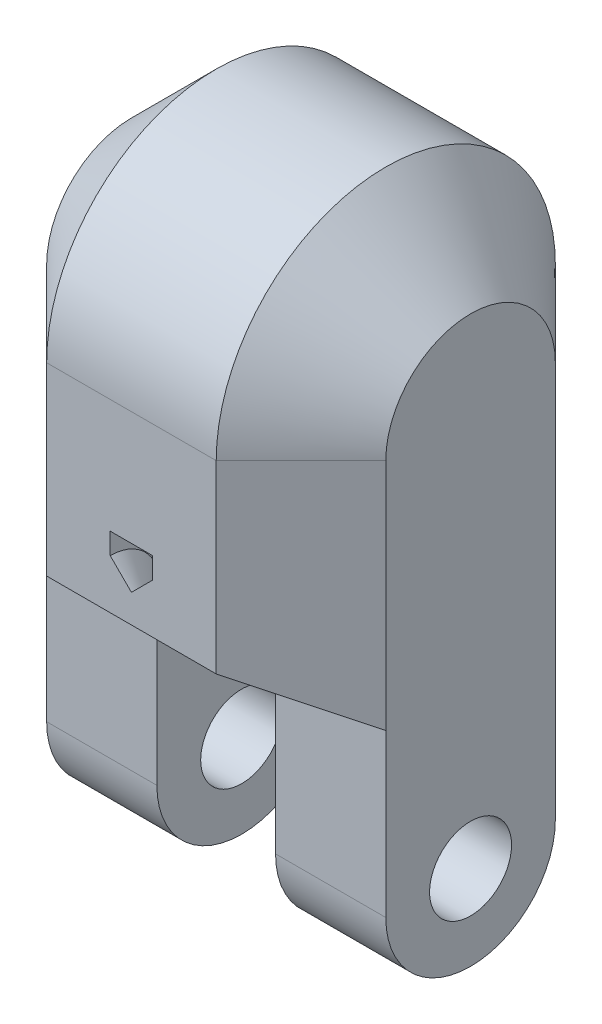
SolidWorks part; units mm, degrees
ref_plane "Front Plane" through (0, 0, 0) normal (0, 0, 1) x (1, 0, 0)
ref_plane "Top Plane" through (0, 0, 0) normal (0, 1, 0) x (1, 0, 0)
ref_plane "Right Plane" through (0, 0, 0) normal (1, 0, 0) x (0, 0, -1)
sketch "Sketch2" plane through (0, 0, 0) normal (0, 1, 0) x (1, 0, 0)
  line L0 (-3, 6) -> (3, 6)
  line L1 (3, 6) -> (6, 3)
  line L2 (6, 3) -> (6, -3)
  line L3 (6, -3) -> (3, -6)
  line L4 (3, -6) -> (-3, -6)
  line L5 (-3, -6) -> (-6, -3)
  line L6 (-6, -3) -> (-6, 3)
  line L7 (-6, 3) -> (-3, 6)
  point P2 (0, -6)
  point P9 (0, 6)
  point P12 (-6, 0)
  point P13 (6, 0)
  dimension "D1" = 12
  dimension "D2" = 12
  dimension "D3" = 6
  dimension "D4" = 6
  dimension "D5" = 6
extrude "Boss-Extrude1" add sketch "Sketch2" along normal mid plane 10 contours L7 L0 L1 L2 L3 L4 L5 L6
sketch "Sketch22" plane through (0, 0, 0) normal (1, 0, 0) x (0, 0, -1)
  line L0 (0, -5) -> (-6, -5)
  line L1 (3, -5) -> (-3, -5) construction
  line L2 (-6, -5) -> (-6, -1.5359)
  line L3 (-6, 5) -> (-6, -5) construction
  line L4 (-6, -1.5359) -> (0, -5)
  dimension "D1" = 30
extrude "Cut-Extrude8" cut sketch "Sketch22" against normal through all both and the other way through all
sketch "Sketch23" plane through (0, 5, 0) normal (0, 1, 0) x (1, 0, 0)
  line L0 (-6, 0) -> (-6, 3)
  line L1 (-6, -3) -> (-6, 3) construction
  line L2 (-6, 3) -> (-3, 6)
  line L3 (-3, 6) -> (3, 6)
  line L4 (3, 6) -> (6, 3)
  line L5 (6, 3) -> (6, 0)
  line L6 (6, 3) -> (6, -3) construction
  line L7 (6, 0) -> (-6, 0)
revolve "Revolve1" add sketch "Sketch23" angle 180 about L7 reverse direction yes
sketch "Sketch24" plane through (0, -5, 0) normal (0, -1, 0) x (1, 0, 0)
  line L1 (-6, -3) -> (-2.1, -3)
  line L2 (-6, -3) -> (-6, 3)
  line L3 (-6, 3) -> (-2.1, 3)
  line L4 (-2.1, -3) -> (-2.1, 3)
  dimension "D1" = 3.9
extrude "Boss-Extrude2" add sketch "Sketch24" along normal mid plane 8
sketch "Sketch25" plane through (0, -9, 0) normal (0, -1, 0) x (1, 0, 0)
  line L0 (-6, 3) -> (-6, -3) construction
  line L2 (-6, 0) -> (-6, 3)
  line L3 (-6, 3) -> (-2.1, 3)
  line L4 (-2.1, 0) -> (-2.1, 3)
  line L5 (-6, 0) -> (-2.1, 0)
revolve "Revolve2" add sketch "Sketch25" angle 180 about L5
sketch "Sketch26" plane through (-6, 0, 0) normal (-1, 0, 0) x (0, 0, 1)
  line L0 (-3, -9) -> (3, -9) construction
  circle A0 centre (0, -9) radius 1.45
  dimension "D1" = 2.9
extrude "Cut-Extrude9" cut sketch "Sketch26" against normal through all both and the other way through all
mirror "Mirror1" about plane through (0, 0, 0) normal (1, 0, 0) of "Revolve2", "Cut-Extrude9", "Boss-Extrude2"
sketch "Sketch30" plane through (0, -3.75, 2.1651) normal (0, -0.866, 0.5) x (1, 0, 0)
  line L0 (0, 3.4282) -> (-0.75, 2.6782)
  line L1 (-0.75, 2.6782) -> (-0.75, 1.9282)
  line L2 (-0.75, 1.9282) -> (0.75, 1.9282)
  line L3 (0.75, 1.9282) -> (0.75, 2.6782)
  line L4 (0.75, 2.6782) -> (0, 3.4282)
  line L5 (-3, 4.4282) -> (3, 4.4282) construction
  point P10 (0, 4.4282)
  dimension "D1" = 135
  dimension "D2" = 0.75
  dimension "D3" = 1.5
  dimension "D4" = 1
revolve "Cut-Revolve1" cut sketch "Sketch30" angle 360 about axis through (-6, -1.5359, 6) along (1, 0, 0)
sketch "Sketch34" plane through (0, -5, 0) normal (0, -1, 0) x (1, 0, 0)
  line L0 (-6, -3) -> (-2.1, -3)
  line L1 (-2.1, -3) -> (2.1, -3)
  line L2 (2.1, -3) -> (6, -3)
  line L3 (6, -3) -> (3, -6)
  line L4 (3, -6) -> (-3, -6)
  line L5 (-3, -6) -> (-6, -3)
extrude "Boss-Extrude4" add sketch "Sketch34" along normal blind 3.75
sketch "Sketch35" plane through (0, -8.75, 0) normal (0, -1, 0) x (1, 0, 0)
  line L0 (0, -3.5) -> (-0.75, -4.25)
  line L1 (-0.75, -4.25) -> (-0.75, -5)
  line L2 (-0.75, -5) -> (0.75, -5)
  line L3 (0.75, -5) -> (0.75, -4.25)
  line L4 (0.75, -4.25) -> (0, -3.5)
  line L5 (-3, -6) -> (3, -6) construction
  dimension "D1" = 1.5
  dimension "D2" = 1.5
  dimension "D3" = 1
  dimension "D4" = 135
revolve "Cut-Revolve3" cut sketch "Sketch35" angle 360 about axis through (3, -8.75, -6) along (1, 0, 0)
